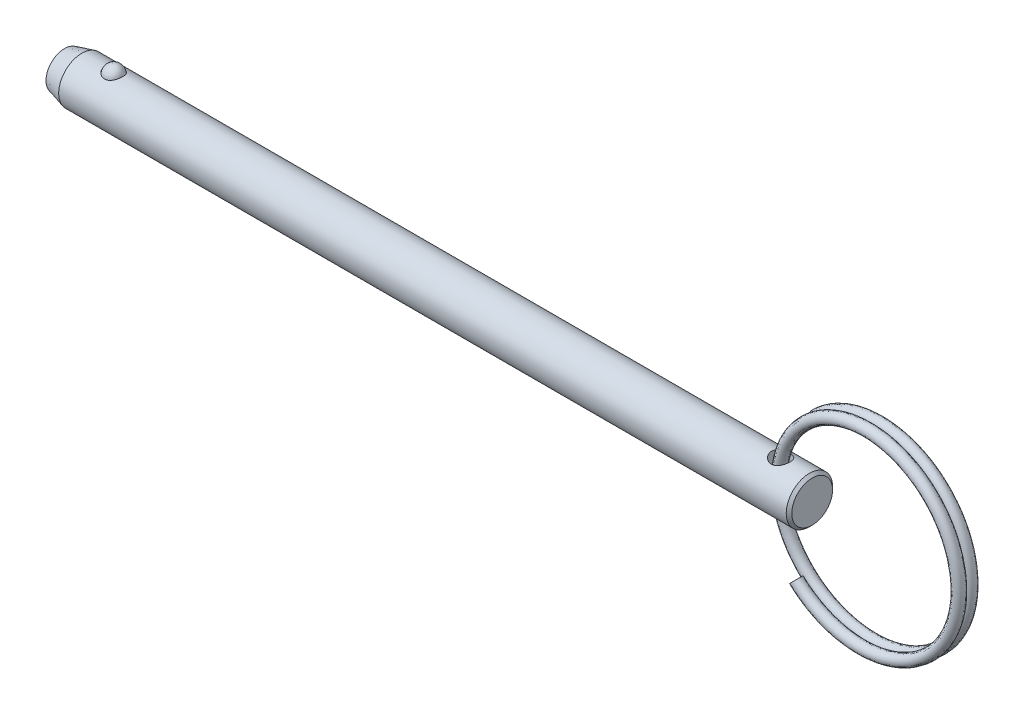
SolidWorks part; units mm, degrees
material "Plain Carbon Steel"
ref_plane "Front" through (0, 0, 0) normal (0, 0, 1) x (1, 0, 0)
ref_plane "Top" through (0, 0, 0) normal (0, 1, 0) x (1, 0, 0)
ref_plane "Right" through (0, 0, 0) normal (1, 0, 0) x (0, 0, -1)
sketch "Sketch1" plane through (0, 0, 0) normal (0, 0, 1) x (1, 0, 0)
  line L0 (51.2064, 2.794) -> (50.8254, 3.175)
  line L1 (50.8254, 3.175) -> (51.2064, 3.175) construction
  line L4 (51.2064, 2.794) -> (51.2064, 0)
  line L5 (51.2064, 3.175) -> (51.2064, 2.794) construction
  line L16 (50.8254, 3.175) -> (-48.8365, 3.175)
  line L17 (-51.2064, 3.175) -> (-51.2064, 2.54) construction
  line L19 (-48.8365, 3.175) -> (-51.2064, 3.175) construction
  line L22 (-51.2064, -3.175) -> (-48.8365, -3.175) construction
  line L23 (-44.4719, 2.8575) -> (-44.4719, -2.8575) construction
  line L24 (-51.2064, 0) -> (51.2064, 0)
  line L27 (51.2064, 0) -> (54.0004, 0) construction
  line L29 (-51.2064, 0) -> (-51.2064, -2.54) construction
  line L36 (45.6184, 0) -> (45.6184, 3.175) construction
  line L37 (-51.2064, 2.54) -> (-51.2064, 0)
  line L38 (-48.8365, -3.175) -> (51.2064, -3.175) construction
  line L39 (-51.2064, -2.54) -> (-51.2064, -3.175) construction
  line L40 (-48.8365, 3.175) -> (-51.2064, 2.54)
  line L42 (-48.8365, -3.175) -> (-51.2064, -2.54) construction
  line L43 (-48.8365, 3.175) -> (-48.8365, -3.175) construction
  circle A2 centre (-44.4719, 2.8575) radius 1.2319 construction
  point P35 (-43.2816, 3.175)
  dimension "A1" = 15
revolve "Revolve1" add sketch "Sketch1" angle 360 about L27
sketch "Sketch2" plane through (0, 0, 0) normal (0, 0, 1) x (1, 0, 0)
  line L0 (-43.2146, 2.8575) -> (-45.7292, 2.8575)
  line L1 (-44.4719, 4.0894) -> (-44.4719, 4.1148) construction
  line L2 (-43.2146, 2.8575) -> (-40.7, 2.8575) construction
  circle A0 centre (-44.4719, 2.8575) radius 1.2319 construction
  circle A1 centre (-44.4719, 2.8575) radius 1.2319 construction
  arc A2 (-45.7292, 2.8575) -> (-43.2146, 2.8575) centre (-44.4719, 2.8575) cw
  dimension "D1" = 0.0254
revolve "Cut-Revolve1" cut sketch "Sketch2" angle 360 about L2
sketch "Sketch3" plane through (0, 0, 0) normal (0, 0, 1) x (1, 0, 0)
  line L0 (-43.24, 2.8575) -> (-45.7038, 2.8575)
  line L1 (-43.24, 2.8575) -> (-40.7762, 2.8575) construction
  circle A0 centre (-44.4719, 2.8575) radius 1.2319 construction
  arc A1 (-43.24, 2.8575) -> (-45.7038, 2.8575) centre (-44.4719, 2.8575) ccw
revolve "Revolve2" add sketch "Sketch3" angle 360 about L1
sketch "Sketch4" plane through (0, 0, 0) normal (0, 0, 1) x (1, 0, 0)
  line L1 (46.8884, -3.175) -> (48.1584, -3.175)
  line L2 (46.8884, -3.175) -> (46.8884, 3.175)
  line L3 (46.8884, 3.175) -> (48.1584, 3.175)
  line L4 (48.1584, -3.175) -> (48.1584, 3.175)
  line L5 (46.8884, -3.175) -> (46.8884, -4.445) construction
  line L6 (48.1584, 3.175) -> (51.2064, 3.175) construction
  line L8 (45.6184, -3.175) -> (45.6184, 3.175) construction
  line L9 (45.6184, 0) -> (46.8884, 0) construction
  line L11 (46.8884, 0) -> (48.1584, 0) construction
  line L12 (50.8254, 3.175) -> (-48.8365, 3.175) construction
  line L14 (-48.8365, -3.175) -> (51.2064, -3.175) construction
  dimension "D1" = 2.54
revolve "Cut-Revolve2" cut sketch "Sketch4" angle 360 about L2
sketch "Sketch5" plane through (0, 0, 0) normal (0, 0, 1) x (1, 0, 0)
  line L0 (0, 0) -> (45.9114, 0) construction
  line L1 (45.9114, 0) -> (45.9114, 3.175) construction
  line L2 (50.8254, 3.175) -> (-48.8365, 3.175) construction
  line L3 (59.3734, 0) -> (72.8354, 0) construction
  line L4 (48.1584, 3.175) -> (47.8654, 3.175) construction
  line L5 (46.8884, 3.175) -> (48.1584, 3.175) construction
  line L6 (46.2912, 3.175) -> (46.2912, -3.175) construction
  line L7 (45.9114, 3.175) -> (45.6184, 3.175) construction
  line L8 (46.8884, -3.175) -> (48.1584, -3.175) construction
  line L9 (46.2912, -3.175) -> (48.1584, -3.175) construction
  line L10 (45.9114, 0) -> (59.3734, 0) construction
  line L12 (47.8654, 3.175) -> (46.2912, 3.175) construction
  line L13 (59.3734, 11.938) -> (59.3734, 13.462) construction
  circle A0 centre (59.3734, 0) radius 13.462
  circle A1 centre (59.3734, 0) radius 11.938 construction
  circle A2 centre (59.3734, 0) radius 12.7 construction
  point P26 (59.3734, 12.7)
curve "Helix/Spiral1" pitch 1.5494 height 1.3557 radius 13.462 left hand yes centre (59.3734, 0, 0) axis (0, 0, -1) start towards (1, 0, 0)
sketch "Sketch6" plane through (114.0038, 0, 0) normal (0, 1, 0) x (0, 0, -1)
  line L0 (0, 66.5684) -> (0, 67.3304) construction
  line L1 (0, 67.3304) -> (0, 68.0924) construction
  circle A0 centre (0, 67.3304) radius 0.762
  dimension "D1" = 1.524
sketch "Sketch7" plane through (0, 0, 0) normal (0, 0, 1) x (1, 0, 0)
  circle A0 centre (59.3734, 0) radius 13.462 construction
  circle A1 centre (59.3734, 0) radius 13.462
curve "Helix/Spiral2" pitch 1.5494 height 1.3557 radius 13.462 left hand yes centre (59.3734, 0, 0) axis (0, 0, 1) start towards (1, 0, 0)
sweep "Sweep1" add profiles "Sketch6" path "Helix/Spiral1"
sweep "Sweep2" add profiles "Sketch6<2>" path "Helix/Spiral2"
sketch "Sketch6<2>" plane through (114.0038, 0, 0) normal (0, 1, 0) x (0, 0, -1) same geometry as "Sketch6"
equation "\"D12@Sketch1\"=\"A@Sketch1\" * 0.80"
equation "\"D2@Sketch1\"=\"A@Sketch1\" * 0.9"
equation "\"D1@Sketch4\" = \"A@Sketch1\" / 2.5"
equation "\"Ring OD@Sketch5\" = \"R Ring Dia@Sketch5\" * 0.06"
equation "\"D4@Helix/Spiral1\"=\"Ring OD@Sketch5\" + 0.001"
equation "\"D1@Sketch6\"=\"Ring OD@Sketch5\""
equation "\"D4@Helix/Spiral2\" = \"D4@Helix/Spiral1\""
equation "\"D5@Helix/Spiral2\" = \"D5@Helix/Spiral1\""
